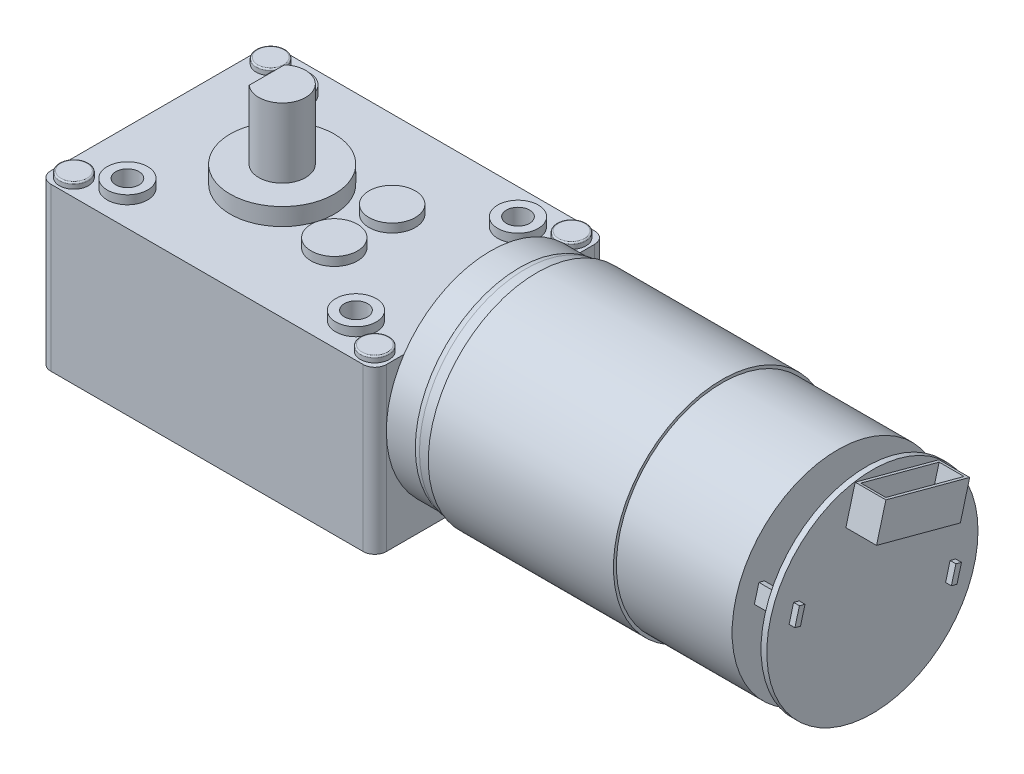
SolidWorks part; units mm, degrees
ref_plane "Alzado" through (0, 0, 0) normal (0, 0, 1) x (1, 0, 0)
ref_plane "Planta" through (0, 0, 0) normal (0, 1, 0) x (1, 0, 0)
ref_plane "Vista lateral" through (0, 0, 0) normal (1, 0, 0) x (0, 0, -1)
sketch "Croquis1" plane through (0, 0, 0) normal (0, 1, 0) x (1, 0, 0)
  line L1 (-29, -20) -> (29, -20)
  line L2 (-29, -20) -> (-29, 20)
  line L3 (-29, 20) -> (29, 20)
  line L4 (29, -20) -> (29, 20)
  line L5 (-29, -20) -> (29, 20) construction
  line L6 (-29, 20) -> (29, -20) construction
  point P0 (0, 0)
  dimension "D1" = 58
  dimension "D2" = 40
extrude "Saliente-Extruir1" add sketch "Croquis1" along normal blind 28
sketch "Croquis2" plane through (0, 28, 0) normal (0, 1, 0) x (1, 0, 0)
  line L0 (-29, 20) -> (-29, -20) construction
  line L1 (-29, -20) -> (29, -20) construction
  line L2 (29, 20) -> (-29, 20) construction
  line L3 (29, -20) -> (29, 20) construction
  circle A0 centre (-26, 17) radius 2.5
  circle A1 centre (26, 17) radius 2.5
  circle A2 centre (26, -17) radius 2.5
  circle A3 centre (-26, -17) radius 2.5
  dimension "D1" = 5
  dimension "D2" = 5
  dimension "D3" = 5
  dimension "D4" = 5
  dimension "D5" = 3
  dimension "D6" = 3
  dimension "D7" = 3
  dimension "D8" = 3
  dimension "D9" = 3
  dimension "D10" = 3
  dimension "D11" = 3
  dimension "D12" = 3
extrude "Saliente-Extruir2" add sketch "Croquis2" along normal blind 1
sketch "Croquis3" plane through (0, 28, 0) normal (0, 1, 0) x (1, 0, 0)
  line L1 (-19.75, -14) -> (19.75, -14)
  line L2 (-19.75, -14) -> (-19.75, 14)
  line L3 (-19.75, 14) -> (19.75, 14)
  line L4 (19.75, -14) -> (19.75, 14)
  line L5 (-19.75, -14) -> (19.75, 14) construction
  line L6 (-19.75, 14) -> (19.75, -14) construction
  circle A0 centre (-19.75, 14) radius 3.5
  circle A1 centre (-19.75, -14) radius 3.5
  circle A2 centre (19.75, -14) radius 3.5
  circle A3 centre (19.75, 14) radius 3.5
  circle A4 centre (-19.75, -14) radius 2
  circle A5 centre (-19.75, 14) radius 2
  circle A6 centre (19.75, 14) radius 2
  circle A7 centre (19.75, -14) radius 2
  point P0 (0, 0)
  dimension "D3" = 7
  dimension "D4" = 7
  dimension "D5" = 7
  dimension "D6" = 7
  dimension "D7" = 4
  dimension "D8" = 4
  dimension "D9" = 4
  dimension "D10" = 4
  dimension "D1" = 28
  dimension "D2" = 39.5
extrude "Saliente-Extruir3" add sketch "Croquis3" along normal blind 1.5 contours A5 L3 A0 L2 | A5 L2 A0 L3 | A4 L2 A1 L1 | A4 L1 A1 L2 | A7 L1 A2 L4 | A7 L4 A2 L1 | A6 L4 A3 L3 | A6 L3 A3 L4 region at (-17.9559, 28, 12.2059) region at (-17, 28, 14.099) region at (17.9559, 28, 12.2059) region at (17, 28, 14.099) region at (-22.1549, 28, -16.4049) region at (-17.9559, 28, -12.2059) region at (17.9559, 28, -12.2059) region at (19.849, 28, -11.25)
sketch "Croquis4" plane through (0, 28, 0) normal (0, 1, 0) x (1, 0, 0)
  line L0 (-29, 20) -> (-29, -20) construction
  circle A0 centre (-7, 0) radius 9
  circle A1 centre (-7, 0) radius 4.05
  dimension "D1" = 8.1
  dimension "D2" = 18
  dimension "D3" = 22
extrude "Saliente-Extruir4" add sketch "Croquis4" along normal blind 3
sketch "Croquis5" plane through (0, 28, 0) normal (0, 1, 0) x (1, 0, 0)
  line L0 (-2.9759, 0) -> (42.8534, 0) construction
  circle A0 centre (7, 5) radius 4
  circle A1 centre (7, -5) radius 4
  dimension "D1" = 8
  dimension "D2" = 5
  dimension "D3" = 7
extrude "Saliente-Extruir5" add sketch "Croquis5" along normal blind 1.5
fillet "Redondeo1" radius 0.25 4 edges at (26, 29, -14.5) (26, 29, 19.5) (-26, 29, 19.5) (-26, 29, -14.5)
fillet "Redondeo2" radius 0.1 4 edges at (19.75, 29.5, -10.5) (19.75, 29.5, 17.5) (-19.75, 29.5, -10.5) (-19.75, 29.5, 17.5)
fillet "Redondeo3" radius 2 4 edges at (-29, 14, -20) (29, 14, -20) (29, 14, 20) (-29, 14, 20)
sketch "Croquis7" plane through (0, 29.5, 0) normal (0, 1, 0) x (1, 0, 0)
  circle A0 centre (-19.75, 14) radius 2
  circle A1 centre (-19.75, 14) radius 3.5
  circle A2 centre (-19.75, -14) radius 2
  circle A3 centre (-19.75, -14) radius 3.5
  circle A4 centre (19.75, -14) radius 2
  circle A5 centre (19.75, -14) radius 3.5
  circle A6 centre (19.75, 14) radius 2
  circle A7 centre (19.75, 14) radius 3.5
extrude "Saliente-Extruir6" add sketch "Croquis7" against normal blind 31
sketch "Croquis8" plane through (0, 31, 0) normal (0, 1, 0) x (1, 0, 0)
  circle A0 centre (-7, 0) radius 4.05
  circle A1 centre (-7, 0) radius 9
extrude "Saliente-Extruir7" add sketch "Croquis8" against normal blind 33.5
sketch "Croquis9" plane through (0, 29.5, 0) normal (0, 1, 0) x (1, 0, 0)
  circle A0 centre (7, 5) radius 4
  circle A1 centre (7, -5) radius 4
extrude "Saliente-Extruir8" add sketch "Croquis9" against normal blind 30.5
sketch "Croquis10" plane through (0, 28, 0) normal (0, 1, 0) x (1, 0, 0)
  circle A0 centre (-19.75, 14) radius 2
  circle A1 centre (-19.75, -14) radius 2
  circle A2 centre (19.75, -14) radius 2
  circle A3 centre (19.75, 14) radius 2
extrude "Cortar-Extruir1" cut sketch "Croquis10" against normal blind 30.5
sketch "Croquis11" plane through (0, 28, 0) normal (0, 1, 0) x (1, 0, 0)
  line L0 (-9.6548, 3.0585) -> (-9.6548, -3.0585)
  arc A0 (-9.6548, -3.0585) -> (-9.6548, 3.0585) centre (-7, 0) ccw
extrude "Saliente-Extruir9" add sketch "Croquis11" along normal blind 15
sketch "Croquis12" plane through (29, 0, 0) normal (1, 0, 0) x (0, 0, -1)
  line L0 (-18, 0) -> (18, 0) construction
  circle A0 centre (0, 18) radius 18
  dimension "D1" = 36
  dimension "D2" = 18
extrude "Saliente-Extruir10" add sketch "Croquis12" along normal blind 5
sketch "Croquis13" plane through (34, 0, 0) normal (1, 0, 0) x (0, 0, -1)
  circle A0 centre (0, 18) radius 18.25
  dimension "D1" = 36.5
extrude "Saliente-Extruir11" add sketch "Croquis13" along normal blind 3
fillet "Redondeo4" radius 2 1 edges at (34, 18, -18.25)
sketch "Croquis14" plane through (37, 0, 0) normal (1, 0, 0) x (0, 0, -1)
  circle A0 centre (0, 18) radius 18.75
  dimension "D1" = 37.5
extrude "Saliente-Extruir12" add sketch "Croquis14" along normal blind 32
sketch "Croquis15" plane through (69, 0, 0) normal (1, 0, 0) x (0, 0, -1)
  circle A0 centre (0, 18) radius 18.25
  dimension "D1" = 36.5
extrude "Saliente-Extruir13" add sketch "Croquis15" along normal blind 20
sketch "Croquis16" plane through (89, 0, 0) normal (1, 0, 0) x (0, 0, -1)
  line L0 (-28.7155, 18) -> (32.6561, 18) construction
  line L1 (-14.3942, 20.304) -> (-13.4282, 20.0452)
  line L2 (-14.3942, 20.304) -> (-13.6177, 23.2018)
  line L3 (-13.6177, 23.2018) -> (-12.6518, 22.9429)
  line L4 (-13.4282, 20.0452) -> (-12.6518, 22.9429)
  line L5 (-14.3942, 20.304) -> (-12.6518, 22.9429) construction
  line L6 (-13.6177, 23.2018) -> (-13.4282, 20.0452) construction
  line L7 (-35.5758, 27.5325) -> (0, 18) construction
  line L8 (0, 18) -> (8.9741, 51.4919) construction
  line L9 (14.3942, 15.696) -> (12.6518, 13.0571) construction
  line L10 (13.6177, 12.7982) -> (13.4282, 15.9548) construction
  line L11 (12.6518, 13.0571) -> (13.4282, 15.9548)
  line L12 (14.3942, 15.696) -> (13.4282, 15.9548)
  line L13 (13.6177, 12.7982) -> (14.3942, 15.696)
  line L14 (13.6177, 12.7982) -> (12.6518, 13.0571)
  point P0 (-13.523, 21.6235)
  point P15 (13.523, 14.3765)
  dimension "D1" = 3
  dimension "D2" = 1
  dimension "D3" = 15
  dimension "D4" = 14
  dimension "D5" = 90
extrude "Saliente-Extruir14" add sketch "Croquis16" along normal blind 5 contours L2 L1 L4 L3 | L11 L12 L13 L14
sketch "Croquis18" plane through (94, 0, 0) normal (1, 0, 0) x (0, 0, -1)
  circle A0 centre (0, 18) radius 18.25
extrude "Saliente-Extruir15" add sketch "Croquis18" along normal blind 1
sketch "Croquis19" plane through (95, 0, 0) normal (1, 0, 0) x (0, 0, -1)
  line L0 (-14.3942, 20.304) -> (-13.6177, 23.2018)
  line L1 (-13.6177, 23.2018) -> (-12.6518, 22.9429)
  line L2 (-12.6518, 22.9429) -> (-13.4282, 20.0452)
  line L3 (-13.4282, 20.0452) -> (-14.3942, 20.304)
  line L4 (13.4282, 15.9548) -> (14.3942, 15.696)
  line L5 (14.3942, 15.696) -> (13.6177, 12.7982)
  line L6 (13.6177, 12.7982) -> (12.6518, 13.0571)
  line L7 (12.6518, 13.0571) -> (13.4282, 15.9548)
extrude "Saliente-Extruir16" add sketch "Croquis19" along normal blind 1
sketch "Croquis20" plane through (95, 0, 0) normal (1, 0, 0) x (0, 0, -1)
  line L0 (-13.04, 21.4941) -> (25.5757, 11.147) construction
  line L1 (11.5144, 31.9946) -> (9.9049, 25.9879)
  line L2 (11.5144, 31.9946) -> (-2.9745, 35.8769)
  line L3 (-2.9745, 35.8769) -> (-4.584, 29.8702)
  line L4 (9.9049, 25.9879) -> (-4.584, 29.8702)
  line L5 (11.5144, 31.9946) -> (-4.584, 29.8702) construction
  line L6 (-2.9745, 35.8769) -> (9.9049, 25.9879) construction
  line L7 (-13.4282, 20.0452) -> (-12.6518, 22.9429) construction
  line L8 (7.7849, 47.0538) -> (0, 18) construction
  line L9 (7.7849, 47.0538) -> (-6.5624, -6.4913) construction
  point P0 (3.4652, 30.9324)
  point P12 (3.4652, 30.9324)
  dimension "D1" = 15
  dimension "D2" = 6.2186
  dimension "D3" = 6.2186
  dimension "D4" = 90
extrude "Saliente-Extruir17" add sketch "Croquis20" along normal blind 5.3
sketch "Croquis21" plane through (0, 32.7299, -8.77) normal (0, -0.9659, 0.2588) x (1, 0, 0)
  line L0 (100.3, 12.1587) -> (95, 12.1587) construction
  line L1 (95.5, -2.3413) -> (99.8, -2.3413)
  line L2 (95.5, -2.3413) -> (95.5, 11.6587)
  line L3 (95.5, 11.6587) -> (99.8, 11.6587)
  line L4 (99.8, -2.3413) -> (99.8, 11.6587)
  line L5 (95.5, -2.3413) -> (99.8, 11.6587) construction
  line L6 (95.5, 11.6587) -> (99.8, -2.3413) construction
  line L7 (100.3, -2.8413) -> (95, -2.8413) construction
  line L8 (100.3, 12.1587) -> (100.3, -2.8413) construction
  line L9 (95, 12.1587) -> (95, -2.8413) construction
  point P0 (97.65, 4.6587)
  dimension "D1" = 0.5
  dimension "D2" = 0.5
  dimension "D3" = 0.5
  dimension "D4" = 0.5
extrude "Cortar-Extruir2" cut sketch "Croquis21" along normal blind 6
